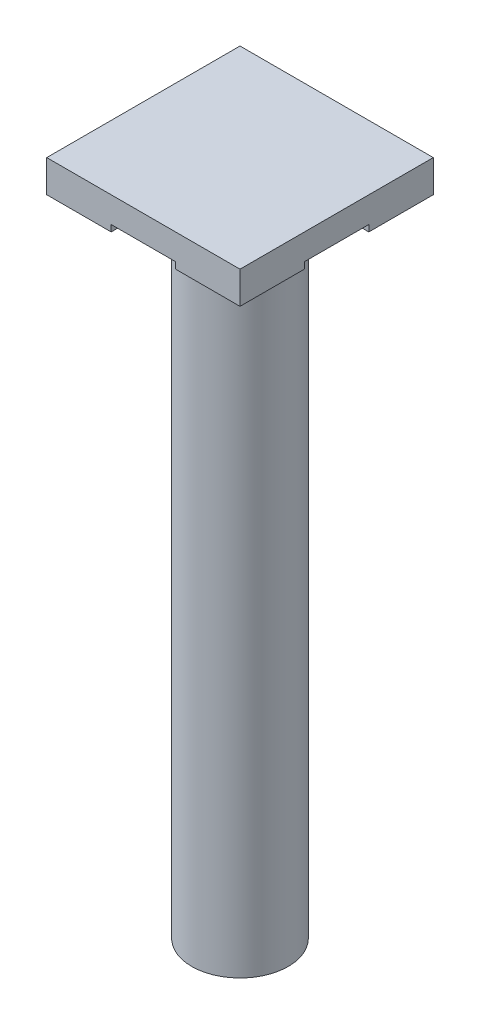
SolidWorks part; units mm, degrees
material "Alumina"
ref_plane "Front Plane" through (0, 0, 0) normal (0, 0, 1) x (1, 0, 0)
ref_plane "Top Plane" through (0, 0, 0) normal (0, 1, 0) x (1, 0, 0)
ref_plane "Right Plane" through (0, 0, 0) normal (1, 0, 0) x (0, 0, -1)
sketch "Sketch1" plane through (0, 0, 0) normal (0, 1, 0) x (1, 0, 0)
  circle A0 centre (0, 0) radius 19.05
  dimension "D1" = 38.1
extrude "Boss-Extrude1" add sketch "Sketch1" along normal blind 254
sketch "Sketch5" plane through (0, 254, 0) normal (0, 1, 0) x (1, 0, 0)
  line L1 (-38.1, 38.1) -> (38.1, 38.1)
  line L2 (-38.1, 38.1) -> (-38.1, -38.1)
  line L3 (-38.1, -38.1) -> (38.1, -38.1)
  line L4 (38.1, 38.1) -> (38.1, -38.1)
  dimension "D1" = 76.2
  dimension "D2" = 76.2
  dimension "D3" = 38.1
  dimension "D4" = 38.1
extrude "Boss-Extrude3" add sketch "Sketch5" along normal blind 12.7
sketch "Sketch6" plane through (0, 254, 0) normal (0, -1, 0) x (1, 0, 0)
  line L0 (-38.1, -38.1) -> (-38.1, 38.1) construction
  line L1 (-38.1, 12.7) -> (-29.21, 12.7)
  line L2 (-38.1, 12.7) -> (-38.1, -12.7)
  line L3 (-38.1, -12.7) -> (-29.21, -12.7)
  line L4 (-29.21, 12.7) -> (-29.21, -12.7)
  line L5 (-38.1, 38.1) -> (38.1, 38.1) construction
  line L6 (-12.7, 38.1) -> (12.7, 38.1)
  line L7 (-12.7, 38.1) -> (-12.7, 29.21)
  line L8 (-12.7, 29.21) -> (12.7, 29.21)
  line L9 (12.7, 38.1) -> (12.7, 29.21)
  line L10 (38.1, 38.1) -> (38.1, -38.1) construction
  line L11 (38.1, 12.7) -> (29.21, 12.7)
  line L12 (38.1, 12.7) -> (38.1, -12.7)
  line L13 (38.1, -12.7) -> (29.21, -12.7)
  line L14 (29.21, 12.7) -> (29.21, -12.7)
  line L15 (38.1, -38.1) -> (-38.1, -38.1) construction
  line L16 (-12.7, -38.1) -> (12.7, -38.1)
  line L17 (-12.7, -38.1) -> (-12.7, -29.21)
  line L18 (-12.7, -29.21) -> (12.7, -29.21)
  line L19 (12.7, -38.1) -> (12.7, -29.21)
  dimension "D1" = 25.4
  dimension "D2" = 25.4
  dimension "D3" = 25.4
  dimension "D4" = 25.4
  dimension "D5" = 25.4
  dimension "D6" = 25.4
  dimension "D7" = 25.4
  dimension "D8" = 25.4
  dimension "D9" = 8.89
  dimension "D10" = 8.89
  dimension "D11" = 8.89
  dimension "D12" = 8.89
extrude "Cut-Extrude1" cut sketch "Sketch6" against normal blind 2.54
sketch "Sketch7" plane through (0, 0, 0) normal (0, -1, 0) x (1, 0, 0)
  circle A0 centre (0, 0) radius 17.78
  dimension "D1" = 35.56
extrude "Cut-Extrude2" cut sketch "Sketch7" against normal up to surface (254 mm away) up to face at (0, 254, 19.05)
